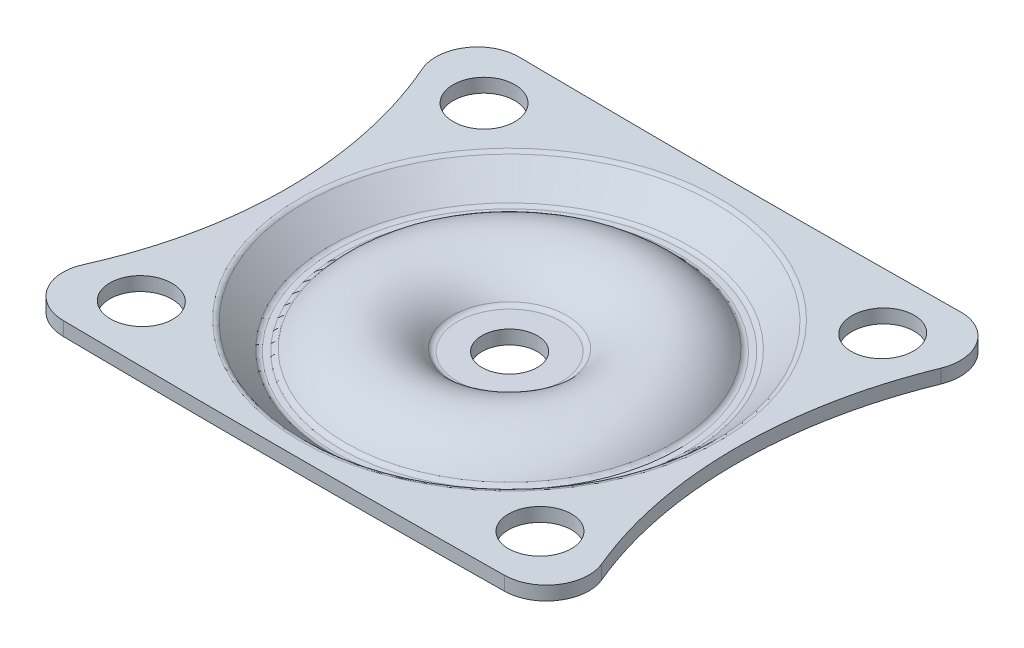
SolidWorks part; units mm, degrees
ref_plane "Alzado" through (0, 0, 0) normal (0, 0, 1) x (1, 0, 0)
ref_plane "Planta" through (0, 0, 0) normal (0, 1, 0) x (1, 0, 0)
ref_plane "Vista lateral" through (0, 0, 0) normal (1, 0, 0) x (0, 0, -1)
sketch "Croquis1" plane through (0, 0, 0) normal (0, 0, 1) x (1, 0, 0)
  line L0 (3.7638, 0) -> (0, 0)
  line L1 (0, -1) -> (15, -1) construction
  line L2 (4.0072, 0) -> (4.0072, 2) construction
  line L3 (12.2252, 0) -> (12.6505, 0)
  line L4 (12.9908, 0.1337) -> (14.8594, 1.8694)
  line L5 (15.1919, 2.003) -> (30.5258, 2.2437)
  line L6 (8, -1) -> (8, 3.9942) construction
  line L7 (4.0072, 2) -> (15, 2) construction
  line L8 (15, -1) -> (15, 4.7358) construction
  line L9 (15.5913, 1.0092) -> (30.5415, 1.2438)
  line L10 (13.6713, -0.599) -> (15.2588, 0.8756)
  line L11 (12.2252, -1) -> (12.6505, -1)
  line L12 (3.7638, -1) -> (0, -1)
  line L13 (30.5258, 2.2437) -> (30.5415, 1.2438)
  line L14 (0, 0) -> (0, -1)
  line L15 (0, -1) -> (0, -11.4008) construction
  line L16 (15.3994, 1.0061) -> (30.5415, 1.2438) construction
  line L17 (13.6713, -0.599) -> (15.3994, 1.0061) construction
  arc A0 (11.8388, 0.1827) -> (4.1502, 0.1827) centre (7.9945, -2.9746) ccw
  arc A1 (4.1502, 0.1827) -> (3.7638, 0) centre (3.7638, 0.5) cw
  arc A2 (12.2252, 0) -> (11.8388, 0.1827) centre (12.2252, 0.5) cw
  arc A3 (15.1919, 2.003) -> (14.8594, 1.8694) centre (15.1997, 1.5031) ccw
  arc A4 (12.9908, 0.1337) -> (12.6505, 0) centre (12.6505, 0.5) cw
  arc A6 (13.6713, -0.599) -> (12.6505, -1) centre (12.6505, 0.5) cw
  arc A7 (12.2252, -1) -> (11.066, -0.452) centre (12.2252, 0.5) cw
  arc A8 (11.066, -0.452) -> (4.923, -0.452) centre (7.9945, -2.9746) ccw
  arc A9 (4.923, -0.452) -> (3.7638, -1) centre (3.7638, 0.5) cw
  arc A10 (15.5913, 1.0092) -> (15.2588, 0.8756) centre (15.5991, 0.5092) ccw
  arc A11 (15.3994, 1.0061) -> (15.3994, 1.0061) centre (15.3994, 1.0061) ccw construction
  dimension "D3" = 15
  dimension "D4" = 0.5
  dimension "D5" = 1
  dimension "D1" = 0.5
  dimension "D2" = 0.5
  dimension "D6" = 0.5
revolve "Revolución1" add sketch "Croquis1" angle 360 about L15
sketch "Croquis2" plane through (0, 0, 0) normal (0, 1, 0) x (1, 0, 0)
  line L0 (-16.25, 0.1743) -> (16.25, 0.1743) construction
  line L1 (-0.5468, 16.6743) -> (0, 0.1743) construction
  line L2 (-15.9602, -16.3257) -> (15.9602, -16.3257)
  line L3 (15.9602, 16.6743) -> (-15.9602, 16.6743)
  line L5 (-41.8276, 36.0763) -> (41.8276, 36.0763)
  line L6 (-41.8276, 36.0763) -> (-41.8276, -35.7277)
  line L7 (-41.8276, -35.7277) -> (41.8276, -35.7277)
  line L8 (41.8276, 36.0763) -> (41.8276, -35.7277)
  line L9 (-41.8276, 36.0763) -> (41.8276, -35.7277) construction
  line L10 (-41.8276, -35.7277) -> (41.8276, 36.0763) construction
  circle A0 centre (-14.4226, 12.5743) radius 2.25
  circle A1 centre (-14.4226, -12.2257) radius 2.253
  arc A2 (-18.7564, -12.0936) -> (-15.9602, -16.3257) centre (-15.9602, -13.2859) ccw
  arc A3 (15.9602, -16.3257) -> (18.7564, -12.0936) centre (15.9602, -13.2859) ccw
  arc A4 (18.7564, 12.4422) -> (18.7564, -12.0936) centre (47.5265, 0.1743) ccw
  arc A5 (18.7564, 12.4422) -> (15.9602, 16.6743) centre (15.9602, 13.6345) ccw
  arc A6 (-15.9602, 16.6743) -> (-18.7564, 12.4422) centre (-15.9602, 13.6345) ccw
  arc A7 (-18.7564, -12.0936) -> (-18.7564, 12.4422) centre (-47.5265, 0.1743) ccw
  circle A8 centre (14.4226, -12.2257) radius 2.253
  circle A9 centre (14.4226, 12.5743) radius 2.25
extrude "Cortar-Extruir4" cut sketch "Croquis2" along normal blind 10 contours L8 L5 L6 L7 A2 A7 A6 L3 A5 A4 A3 L2 region at (0, 0, -34.9739)
extrude "Cortar-Extruir5" cut sketch "Croquis2<6>" along normal blind 10 contours A0 | A1 | A8 | A9 region at (-14.4226, 0, -12.5743) region at (-14.4226, 0, 12.2257) region at (14.4226, 0, 12.2257) region at (14.4226, 0, -12.5743)
sketch "Croquis2<6>" plane through (0, 0, 0) normal (0, 1, 0) x (1, 0, 0) same geometry as "Croquis2"
sketch "Croquis3" plane through (0, 0, 0) normal (0, 1, 0) x (1, 0, 0)
  circle A0 centre (0, 0) radius 2
extrude "Cortar-Extruir6" cut sketch "Croquis3" against normal blind 10
ref_plane "Plano1" through (0, 2.0196, 0) normal (0, 1, 0) x (1, 0, 0)
sketch "Croquis4" plane through (0, 2.0196, 0) normal (0, 1, 0) x (1, 0, 0)
  line L0 (-16.25, 0.1743) -> (16.25, 0.1743)
  arc A0 (-18.7564, -12.0936) -> (-18.7564, 12.4422) centre (-47.5265, 0.1743) ccw construction
  arc A1 (18.7564, 12.4422) -> (18.7564, -12.0936) centre (47.5265, 0.1743) ccw construction
